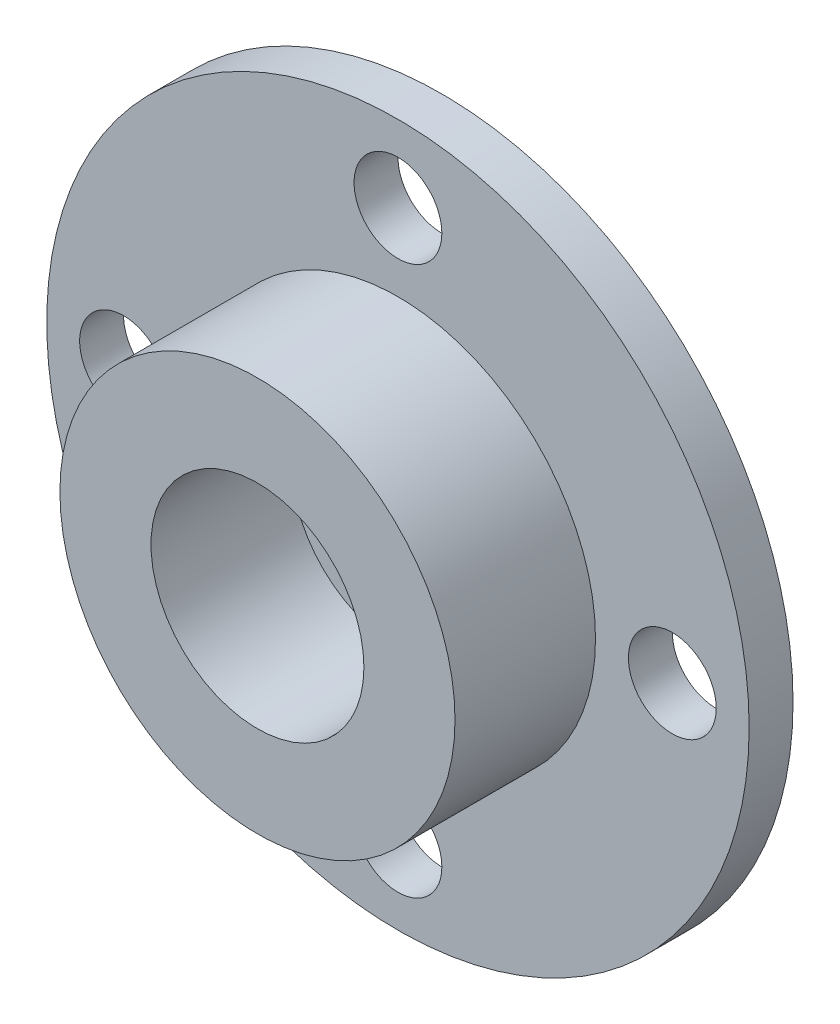
SolidWorks part; units mm, degrees
material "ABS"
ref_plane "Front Plane" through (0, 0, 0) normal (0, 0, 1) x (1, 0, 0)
ref_plane "Top Plane" through (0, 0, 0) normal (0, 1, 0) x (1, 0, 0)
ref_plane "Right Plane" through (0, 0, 0) normal (1, 0, 0) x (0, 0, -1)
sketch "Sketch1" plane through (0, 0, 0) normal (0, 0, 1) x (1, 0, 0)
  line L0 (4.5, 0) -> (8, 0) construction
  circle A0 centre (0, 0) radius 2.425
  circle A1 centre (0, 0) radius 4.5
  circle A2 centre (0, 0) radius 8
  circle A3 centre (6.25, 0) radius 1
  circle A4 centre (0, -6.25) radius 1
  circle A5 centre (-6.25, 0) radius 1
  circle A6 centre (0, 6.25) radius 1
  circle A7 centre (0, 0) radius 1
  point P16 (0, 0)
  point P19 (0, 0)
  dimension "D1" = 4
extrude "Boss-Extrude1" add sketch "Sketch1" along normal blind 3.2 contours A1 A0 region at (-4.3727, 0, 0)
extrude "Boss-Extrude2" add sketch "Sketch1<3>" against normal blind 1 contours A1 A3 A2 A6 A5 A4 | A1 A0 | A0 A7 region at (-2.3564, 0, 0) region at (-4.3727, 0, 0) region at (-7.7737, 0, 0)
sketch "Sketch1<3>" plane through (0, 0, 0) normal (0, 0, 1) x (1, 0, 0) same geometry as "Sketch1"
sketch "Sketch2" plane through (0, 0, -1) normal (0, 0, -1) x (-1, 0, 0)
  circle A0 centre (0, 0) radius 2
  circle A1 centre (0, 0) radius 3
extrude "Boss-Extrude3" add sketch "Sketch2" along normal blind 1
